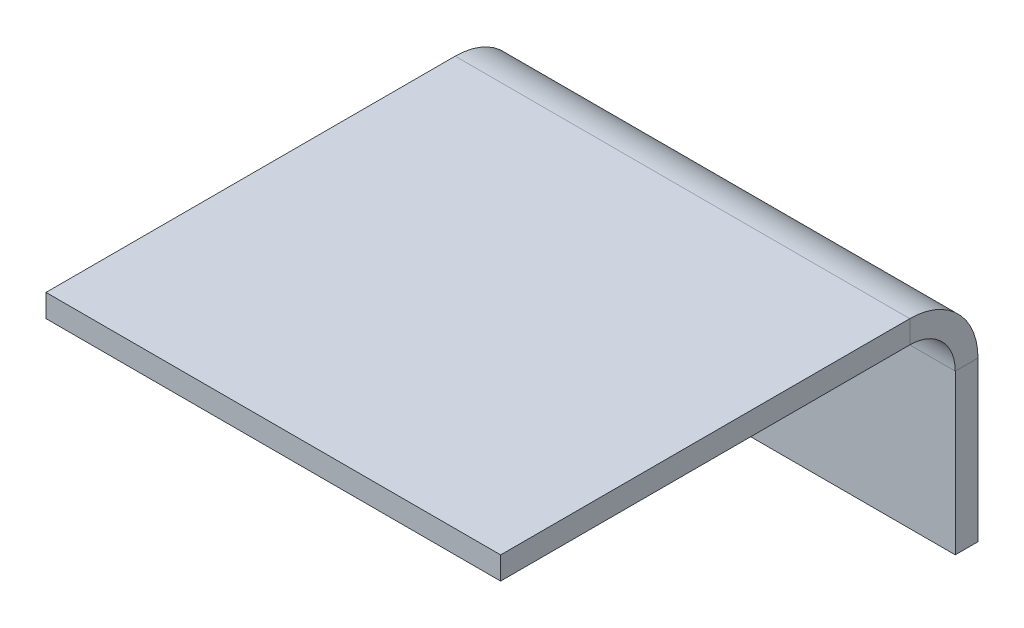
SolidWorks part; units mm, degrees
note: The reader was unsure of these and kept them because the rebuilt part matched: flange length of "EdgeFlange".
ref_plane "前视基准面" through (0, 0, 0) normal (0, 0, 1) x (1, 0, 0)
ref_plane "上视基准面" through (0, 0, 0) normal (0, 1, 0) x (1, 0, 0)
ref_plane "右视基准面" through (0, 0, 0) normal (1, 0, 0) x (0, 0, -1)
other "Configuration Table"
sketch "草图1" plane through (0, 0, 0) normal (0, 0, 1) x (1, 0, 0)
  line L1 (0, 0) -> (20, 0)
  line L2 (0, 0) -> (0, 10)
  line L3 (0, 10) -> (20, 10)
  line L4 (20, 0) -> (20, 10)
base flange "BasePlate" sketch "草图1" thickness 1 reverse thickness direction no parameters "D1"=2
sketch "草图9" plane through (0, 10, 0) normal (0, 1, 0) x (-1, 0, 0)
  line L0 (-20, 0) -> (0, 0) construction
  line L1 (-20, 0) -> (0, 0)
  line L2 (-20, 0) -> (-20, 20)
  line L3 (-20, 20) -> (-18, 20)
  line L4 (-18, 20) -> (-2, 20)
  line L5 (-2, 20) -> (0, 20)
  line L6 (0, 0) -> (0, 20)
edge flange "EdgeFlange" sketch "草图9" flange angle 90 flange length 20 flange position material inside bend radius 2 thickness 1 relief rectangular parameters "D6"=10
bend "边线折弯1" bend radius 2 bend angle 90 parameters "D5"=1
sketch "折弯-线1" plane through (0, 0, 0) normal (0, 1, 0) x (1, 0, 0)
sketch "边界框1" plane through (0, 0, 0) normal (0, 1, 0) x (1, 0, 0)
sheet metal parameters "钣金6" thickness 1 parameters "D1"=2
flat pattern "平板型式6" [suppressed]
sketch "折弯-线2" plane through (0, 0, 0) normal (0, 1, 0) x (1, 0, 0)
sketch "边界框2" [suppressed] plane through (0, 0, 0) normal (0, 1, 0) x (1, 0, 0)
sheet metal parameters "钣金7" thickness 1 parameters "D1"=2
flat pattern "平板型式6" [suppressed]
sketch "折弯-线2" plane through (0, 0, 0) normal (0, 1, 0) x (1, 0, 0)
sketch "边界框2" [suppressed] plane through (0, 0, 0) normal (0, 1, 0) x (1, 0, 0)
bend of the flat pattern "展平-<边线折弯1>1"
